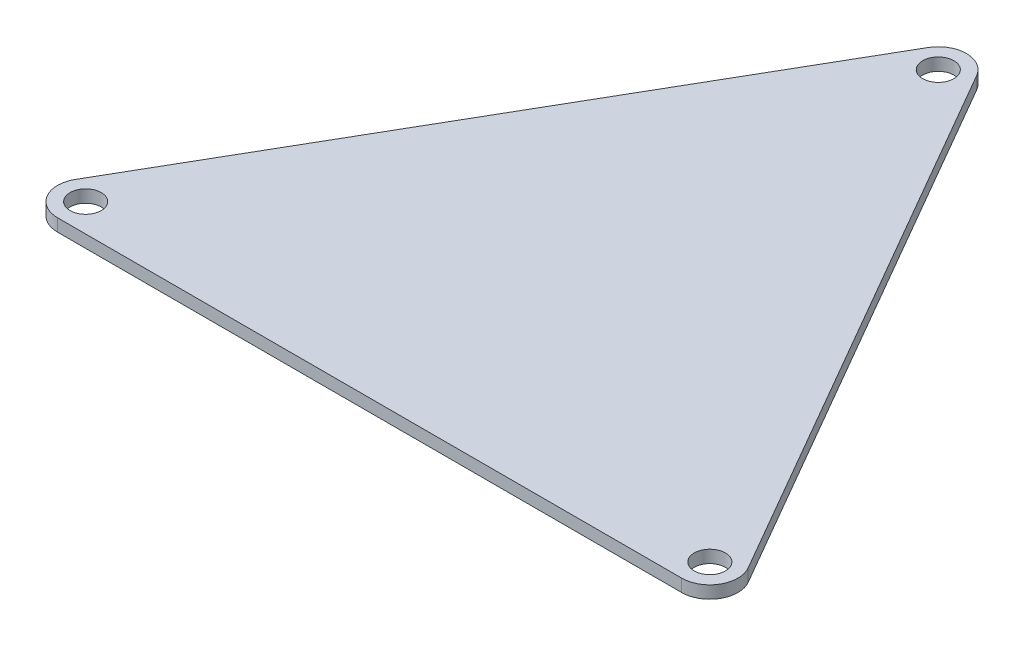
SolidWorks part; units mm, degrees
ref_plane "Front Plane" through (0, 0, 0) normal (0, 0, 1) x (1, 0, 0)
ref_plane "Top Plane" through (0, 0, 0) normal (0, 1, 0) x (1, 0, 0)
ref_plane "Right Plane" through (0, 0, 0) normal (1, 0, 0) x (0, 0, -1)
sketch "Sketch1" plane through (0, 0, 0) normal (0, 1, 0) x (1, 0, 0)
  line L0 (-50, -28.8675) -> (0, 57.735) construction
  line L1 (0, 57.735) -> (50, -28.8675) construction
  line L2 (50, -28.8675) -> (-50, -28.8675) construction
  line L5 (-3.8971, 59.985) -> (-53.8971, -26.6175)
  line L6 (53.8971, -26.6175) -> (3.8971, 59.985)
  line L7 (-50, -33.3675) -> (50, -33.3675)
  circle A0 centre (0, 0) radius 28.8675 construction
  arc A1 (3.8971, 59.985) -> (-3.8971, 59.985) centre (0, 57.735) ccw
  arc A2 (50, -33.3675) -> (53.8971, -26.6175) centre (50, -28.8675) ccw
  arc A3 (-53.8971, -26.6175) -> (-50, -33.3675) centre (-50, -28.8675) ccw
  circle A4 centre (0, 57.735) radius 2.5
  circle A5 centre (50, -28.8675) radius 2.5
  circle A6 centre (-50, -28.8675) radius 2.5
  point P18 (0, 0)
  point P23 (0, 0)
  dimension "D2" = 9
  dimension "D5" = 5
  dimension "D1" = 100
  dimension "D3" = 120
  dimension "D4" = 3
  dimension "D6" = 3
extrude "Boss-Extrude1" add sketch "Sketch1" along normal blind 2
